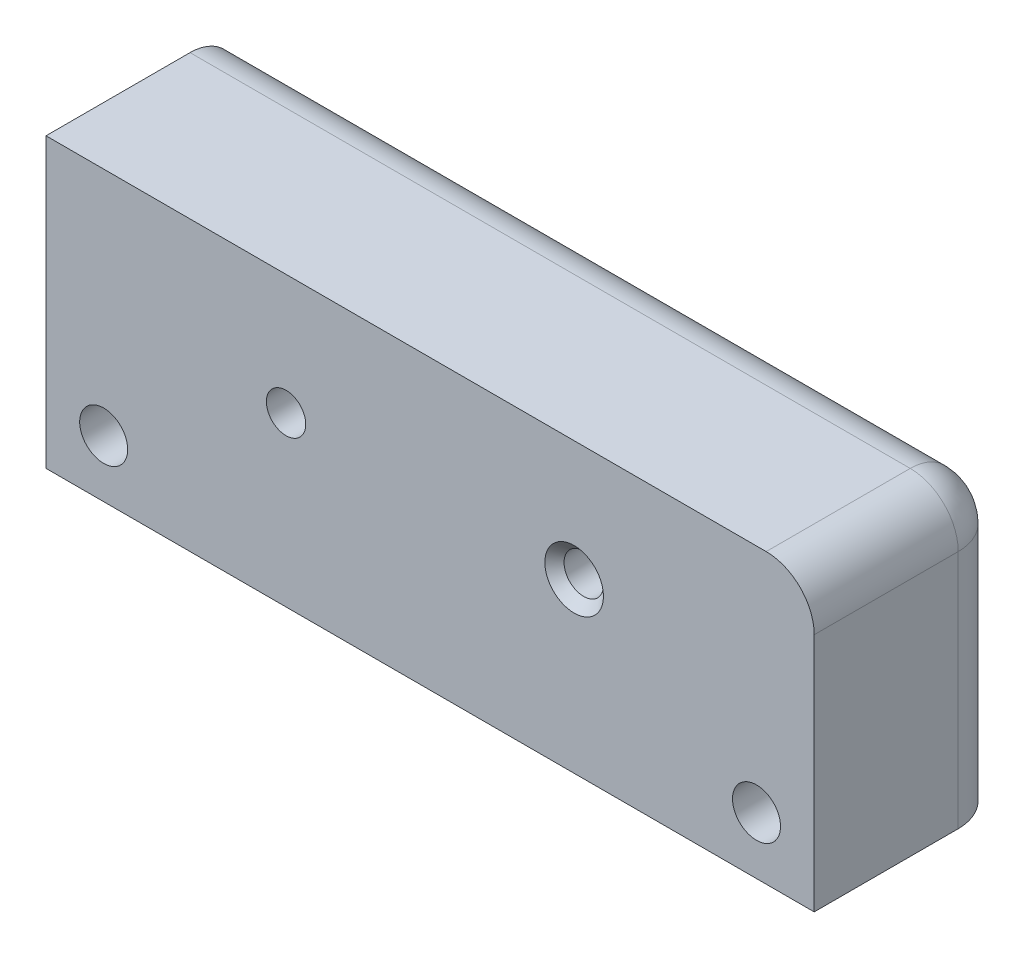
SolidWorks part; units mm, degrees
ref_plane "Front Plane" through (0, 0, 0) normal (0, 0, 1) x (1, 0, 0)
ref_plane "Top Plane" through (0, 0, 0) normal (0, 1, 0) x (1, 0, 0)
ref_plane "Right Plane" through (0, 0, 0) normal (1, 0, 0) x (0, 0, -1)
sketch "Sketch1" plane through (0, 0, 0) normal (0, 1, 0) x (1, 0, 0)
  line L1 (0, 0) -> (80, 0)
  line L2 (0, 0) -> (0, 40)
  line L3 (0, 40) -> (80, 40)
  line L4 (80, 0) -> (80, 40)
  dimension "mD1" = 80
  dimension "mD2" = 40
extrude "cnfBoss-Extrude1" add sketch "Sketch1" along normal blind 60
sketch "Sketch2" plane through (0, 0, 0) normal (0, 0, 1) x (1, 0, 0)
  circle A0 centre (12.0133, 11.9072) radius 5
  dimension "D1" = 10
extrude "cnfCut" cut sketch "Sketch2" against normal through all
hole_wizard "Ø8.2 (8.2) Diameter Hole1" positions "Sketch3" profile "Sketch4" hole size "Ø8.2" standard "ANSI Metric" end condition up to next
sketch "Sketch3" plane through (0, 0, 0) normal (0, 0, 1) x (1, 0, 0)
  line L0 (0, 60) -> (0, 0) construction
  line L1 (0, 0) -> (80, 0) construction
  point P0 (50, 35)
  dimension "cnfD1" = 50
  dimension "cnfD2" = 35
sketch "Sketch4" plane through (50, 35, 0) normal (1, 0, 0) x (0, -1, 0)
  line L0 (0, 0) -> (0, 40)
  line L1 (0, 40) -> (4.1, 40)
  line L2 (4.1, 40) -> (4.1, 0)
  line L5 (4.1, 0) -> (0, 0)
  line L11 (0, -6.35) -> (0, 107.95) construction
  dimension "Thru Hole Dia." = 8.2
  dimension "Thru Hole Depth" = 40
mirror "cnfMirror" about plane through (80, 60, 0) normal (-1, 0, 0) of bodies 103
fillet "cnfFillet" radius 10 1 edges at (160, 30, -40)
fillet "cnfFillet2" radius 10 3 edges at (75, 60, -40) (157.0711, 60, -37.0711) (160, 60, -15)
chamfer "cnfChamfer" distance 2 angle 45 1 edges at (105.9, 35, 0)
